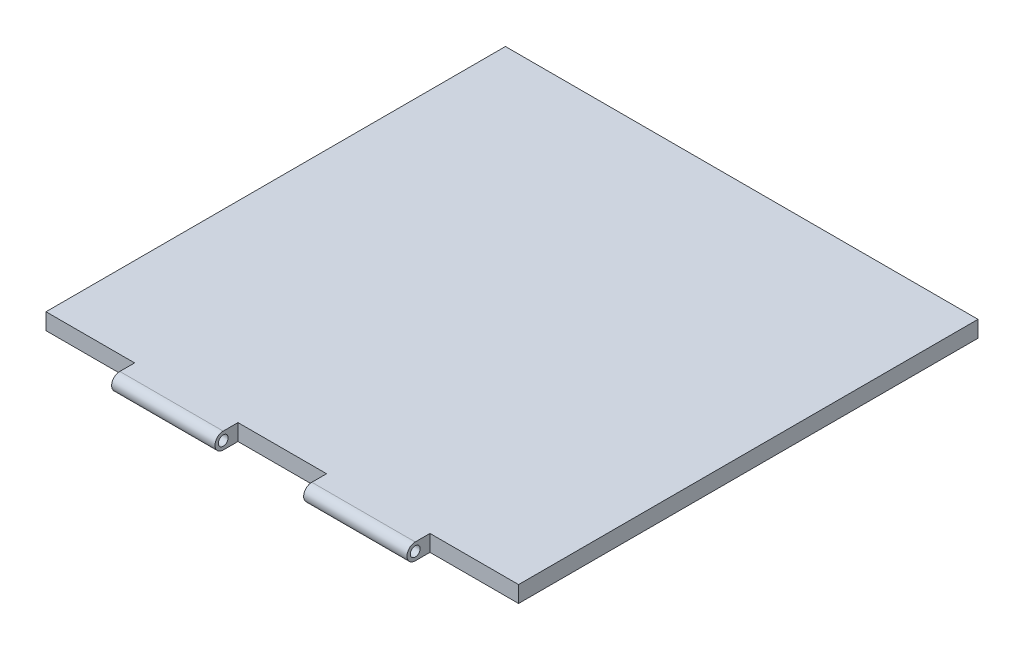
SolidWorks part; units mm, degrees
ref_plane "Front Plane" through (0, 0, 0) normal (0, 0, 1) x (1, 0, 0)
ref_plane "Top Plane" through (0, 0, 0) normal (0, 1, 0) x (1, 0, 0)
ref_plane "Right Plane" through (0, 0, 0) normal (1, 0, 0) x (0, 0, -1)
sketch "Sketch3" plane through (0, 0, 0) normal (1, 0, 0) x (0, 0, -1)
  line L0 (-36.125, 1.3574) -> (36.125, 1.3574)
  line L1 (36.125, 1.3574) -> (36.125, -1.1426)
  line L2 (36.125, -1.1426) -> (-36.125, -1.1426)
  arc A0 (-36.125, -1.1426) -> (-36.125, 1.3574) centre (-36.125, 0.1074) cw
  circle A1 centre (-36.125, 0.1074) radius 0.75
  point P6 (-37.375, 0.1074)
  point P7 (0, 1.3574)
  dimension "D3" = 1.5
  dimension "D1" = 73.5
  dimension "D2" = 2.5
extrude "Boss-Extrude2" add sketch "Sketch3" along normal mid plane 72
sketch "Sketch4" plane through (0, 0, 0) normal (0, 1, 0) x (1, 0, 0)
  line L0 (-36, -37.375) -> (36, -37.375) construction
  line L1 (-36, -33.875) -> (-22.5, -33.875)
  line L2 (-36, -33.875) -> (-36, -37.375)
  line L3 (-36, -37.375) -> (-22.5, -37.375)
  line L4 (-22.5, -33.875) -> (-22.5, -37.375)
  line L5 (36, -36.125) -> (-36, -36.125) construction
  line L6 (36, -33.875) -> (22.5, -33.875)
  line L7 (36, -33.875) -> (36, -37.375)
  line L8 (36, -37.375) -> (22.5, -37.375)
  line L9 (22.5, -33.875) -> (22.5, -37.375)
  line L10 (0, -36.125) -> (0, -15.1444) construction
  line L11 (-36, 36.125) -> (-36, -36.125) construction
  line L12 (-6.75, -33.875) -> (6.75, -33.875)
  line L13 (-6.75, -33.875) -> (-6.75, -37.375)
  line L14 (-6.75, -37.375) -> (6.75, -37.375)
  line L15 (6.75, -33.875) -> (6.75, -37.375)
  line L16 (36, 36.125) -> (36, -36.125) construction
  point P20 (0, -33.875)
  dimension "D1" = 13.5
  dimension "D2" = 13.5
  dimension "D3" = 13.5
  dimension "D4" = 3.5
extrude "Cut-Extrude1" cut sketch "Sketch4" against normal through all both and the other way through all
sketch "Sketch7" plane through (0, 0, 0) normal (1, 0, 0) x (0, 0, -1)
  line L4 (30.8763, -1.1426) -> (30.8763, -3.8787)
  line L5 (-33.875, -1.1426) -> (36.125, -1.1426) construction
  line L6 (30.8763, -3.8787) -> (19.8083, -1.1426)
  line L7 (19.8083, -1.1426) -> (30.8763, -1.1426)
extrude "Boss-Extrude3" add sketch "Sketch7" along normal mid plane 60
equation "\"box_width\"=112"
equation "\"wall\"=2.5"
equation "\"box_length\"= 67"
equation "\"openable_top\"= 72"
equation "\"D1@Sketch3\"=\"openable_top\"+\"wall\"-\"to_fit_in_when_closing\""
equation "\"D2@Sketch3\"=\"wall\""
equation "\"axis_hole\"=1.5"
equation "\"D3@Sketch3\"=\"axis_hole\""
equation "\"D1@Boss-Extrude2\"=\"box_length\"+\"wall\"*2"
equation "\"D4@Sketch4\"=\"wall\"+\"given_to_axis\""
equation "\"given_to_axis\"= 1"
equation "\"to_fit_in_when_closing\"= 1"
